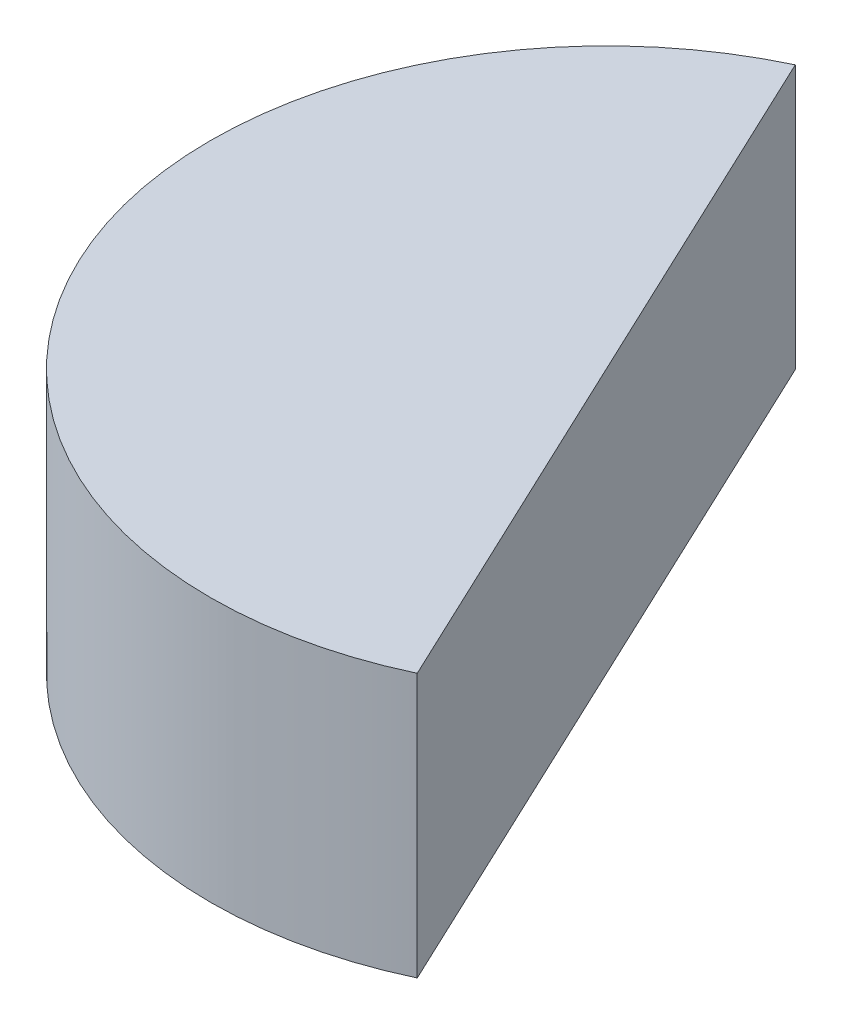
SolidWorks part; units mm, degrees
ref_plane "Front Plane" through (0, 0, 0) normal (0, 0, 1) x (1, 0, 0)
ref_plane "Top Plane" through (0, 0, 0) normal (0, 1, 0) x (1, 0, 0)
ref_plane "Right Plane" through (0, 0, 0) normal (1, 0, 0) x (0, 0, -1)
sketch "Sketch1" plane through (0, 0, 0) normal (0, 1, 0) x (1, 0, 0)
  line L0 (16.2621, -34.4551) -> (-16.2621, 34.4551)
  arc A0 (-16.2621, 34.4551) -> (16.2621, -34.4551) centre (0, 0) ccw
  point P6 (0, 0)
  dimension "D1" = 76.2
extrude "Boss-Extrude1" add sketch "Sketch1" along normal blind 25.4
